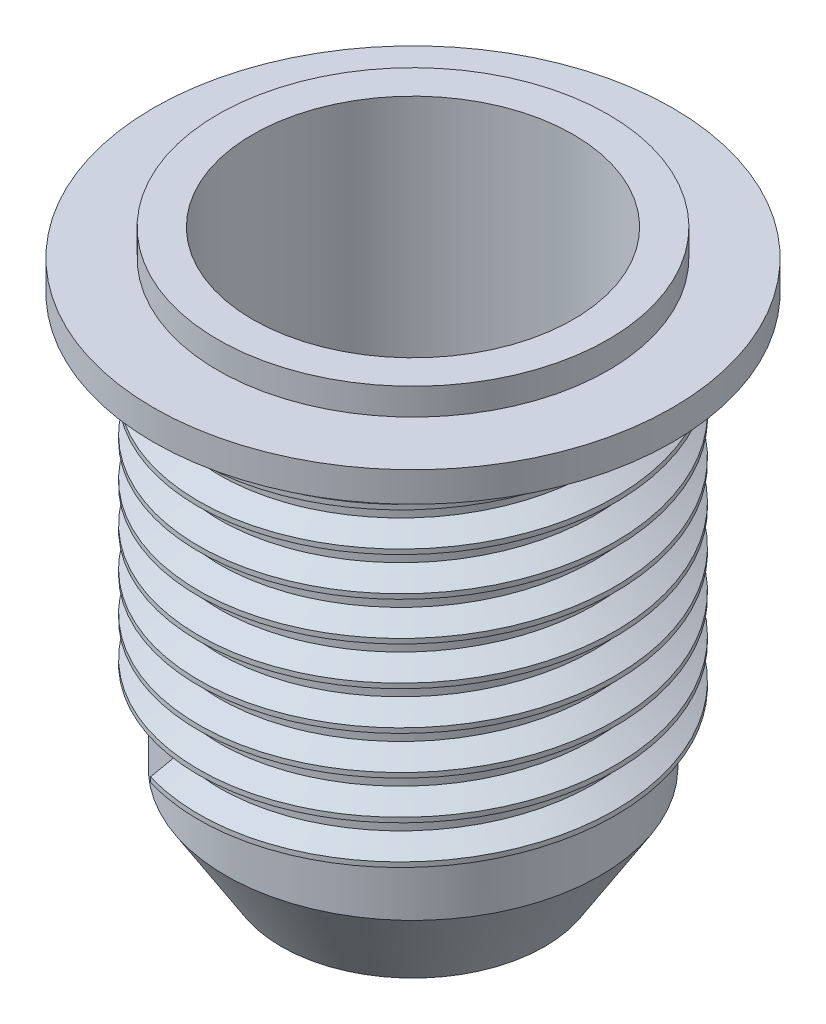
SolidWorks part; units mm, degrees
ref_plane "Front Plane" through (0, 0, 0) normal (0, 0, 1) x (1, 0, 0)
ref_plane "Top Plane" through (0, 0, 0) normal (0, 1, 0) x (1, 0, 0)
ref_plane "Right Plane" through (0, 0, 0) normal (1, 0, 0) x (0, 0, -1)
sketch "Sketch1" plane through (0, 0, 0) normal (0, 0, 1) x (1, 0, 0)
  line L0 (0, 0) -> (0, 55136.1981) construction
  line L1 (6.5719, 0) -> (8.001, 0)
  line L2 (8.001, 0) -> (8.001, -1.0947)
  line L3 (8.001, -1.0947) -> (10.6452, -1.0947)
  line L4 (10.6452, -1.0947) -> (10.6452, -2.3196)
  line L5 (10.6452, -2.3196) -> (7.679, -2.3196)
  line L6 (7.679, -2.3196) -> (7.679, -19.1971)
  line L7 (7.679, -19.1971) -> (5.3964, -22.86)
  line L8 (5.3964, -22.86) -> (4.6278, -22.86)
  line L9 (4.6278, -22.86) -> (6.5719, -19.7403)
  line L10 (6.5719, -19.7403) -> (6.5719, 0)
  point P5 (0, 0)
  point P14 (10.6452, -2.0559)
  point P15 (7.712, -1.7923)
  point P16 (7.679, -2.3196)
  dimension "D1" = 16.002
  dimension "D2" = 22.86
revolve "Revolve1" add sketch "Sketch1" angle 360 about L0
cosmetic thread "Cosmetic Thread1"
thread "Thread2" pitch 1.5875 method extrude profile "Thread Profile2" start angle 0, offset 0, length 13.97, pitch 1.5875, diameter 15.3581
ref_plane "Plane2" through (-7.679, -2.3196, 0) normal (0, 0, 1) x (-1, 0, 0)
sketch "Thread Profile2" plane through (-7.679, -2.3196, 0) normal (0, 0, 1) x (-1, 0, 0)
  line L0 (0, 0) -> (0, 1.5875) construction
  line L1 (0, 0) -> (0.8593, 0.4961)
  line L2 (0.8593, 0.4961) -> (0.8593, 0.6945)
  line L3 (0.8593, 0.6945) -> (0, 1.1906)
  line L4 (0.8593, 0.5953) -> (0, 0.5953) construction
  line L11 (0, 0) -> (0, 1.1906)
  point P2 (0, 0)
  dimension "Pitch" = 1.5875
  dimension "Profile_Angle" = 60
  dimension "Profile_Land" = 0.1984
  dimension "Profile_Height" = 0.8593
